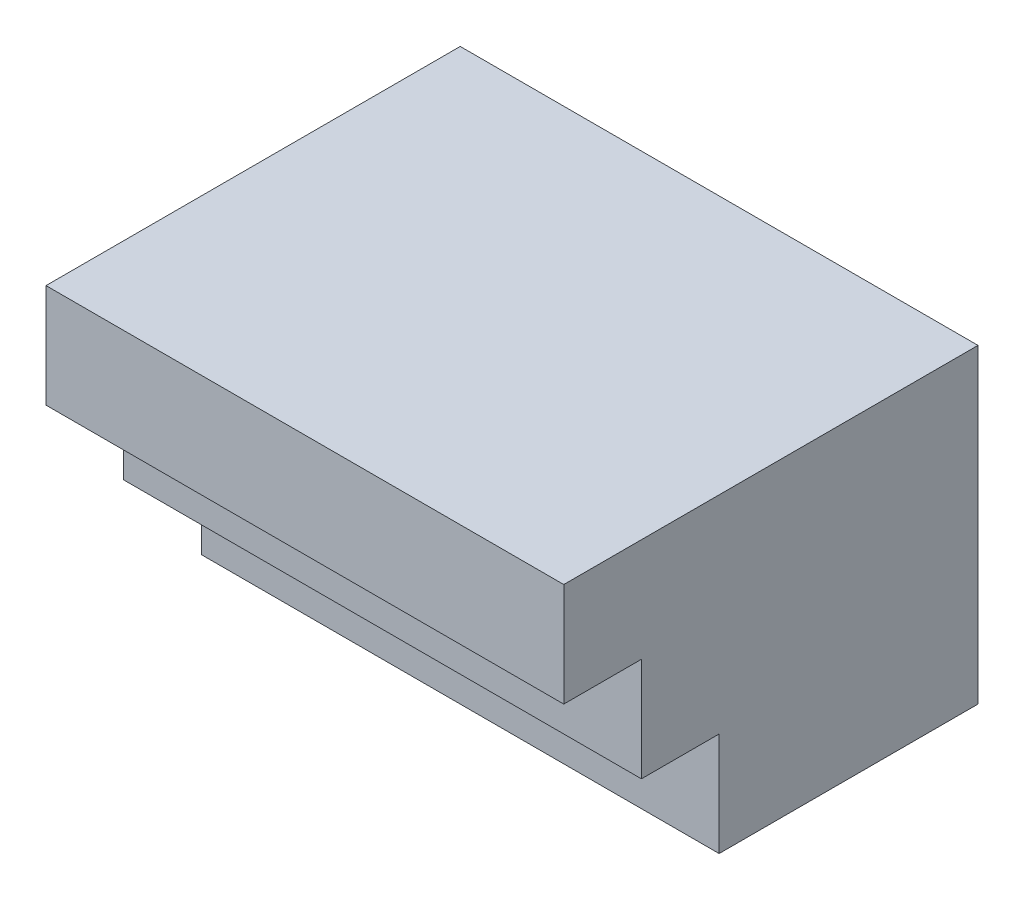
SolidWorks part; units mm, degrees
material "granite"
ref_plane "Front Plane" through (0, 0, 0) normal (0, 0, 1) x (1, 0, 0)
ref_plane "Top Plane" through (0, 0, 0) normal (0, 1, 0) x (1, 0, 0)
ref_plane "Right Plane" through (0, 0, 0) normal (1, 0, 0) x (0, 0, -1)
sketch "Эскиз1" plane through (0, 0, 0) normal (0, 0, 1) x (1, 0, 0)
  line L1 (0, 0) -> (200, 0)
  line L2 (0, 0) -> (0, 40)
  line L3 (0, 40) -> (200, 40)
  line L4 (200, 0) -> (200, 40)
  line L5 (0, 40) -> (200, 40)
  line L6 (0, 40) -> (0, 80)
  line L7 (0, 80) -> (200, 80)
  line L8 (200, 40) -> (200, 80)
extrude "Бобышка-Вытянуть1" add sketch "Эскиз1" along normal blind 100 contours L1 L4 L3 L2 region at (100, 20, 0)
extrude "Бобышка-Вытянуть2" add sketch "Эскиз1<3>" along normal blind 130 contours L3 L8 L7 L6 region at (100, 60, 0)
sketch "Эскиз1<3>" plane through (0, 0, 0) normal (0, 0, 1) x (1, 0, 0) same geometry as "Эскиз1"
sketch "Эскиз9" plane through (-3.1483, 38.9701, 130) normal (0, 0, 1) x (1, 0, 0)
  line L0 (0, 20) -> (200, 20)
  line L1 (0, 0) -> (0, 40) construction
  line L2 (200, 0) -> (200, 40) construction
  circle A0 centre (100, 20) radius 5
  circle A1 centre (42.4712, 20) radius 5
  circle A2 centre (157.5116, 20) radius 5
extrude "Вырез-Вытянуть4" cut sketch "Эскиз9" against normal blind 35 draft 1 contours A1
extrude "Вырез-Вытянуть5" cut sketch "Эскиз9<3>" against normal blind 25 draft 1 contours L0 A2 | L0 A2 region at (154.3633, 61.0922, 130) region at (154.3633, 56.8481, 130)
sketch "Эскиз9<3>" plane through (-3.1483, 38.9701, 130) normal (0, 0, 1) x (1, 0, 0) same geometry as "Эскиз9"
extrude "Вырез-Вытянуть6" cut sketch "Эскиз9<4>" against normal blind 30 draft 1 contours L0 A0 | L0 A0 region at (96.8517, 61.0922, 130) region at (96.8517, 56.8481, 130)
sketch "Эскиз9<4>" plane through (-3.1483, 38.9701, 130) normal (0, 0, 1) x (1, 0, 0) same geometry as "Эскиз9"
sketch "Эскиз10" plane through (0, 0, 0) normal (0, 0, -1) x (-1, 0, 0)
  line L1 (0, 80) -> (-200, 80)
  line L2 (0, 80) -> (0, 120)
  line L3 (0, 120) -> (-200, 120)
  line L4 (-200, 80) -> (-200, 120)
extrude "Бобышка-Вытянуть3" add sketch "Эскиз10" against normal blind 160
